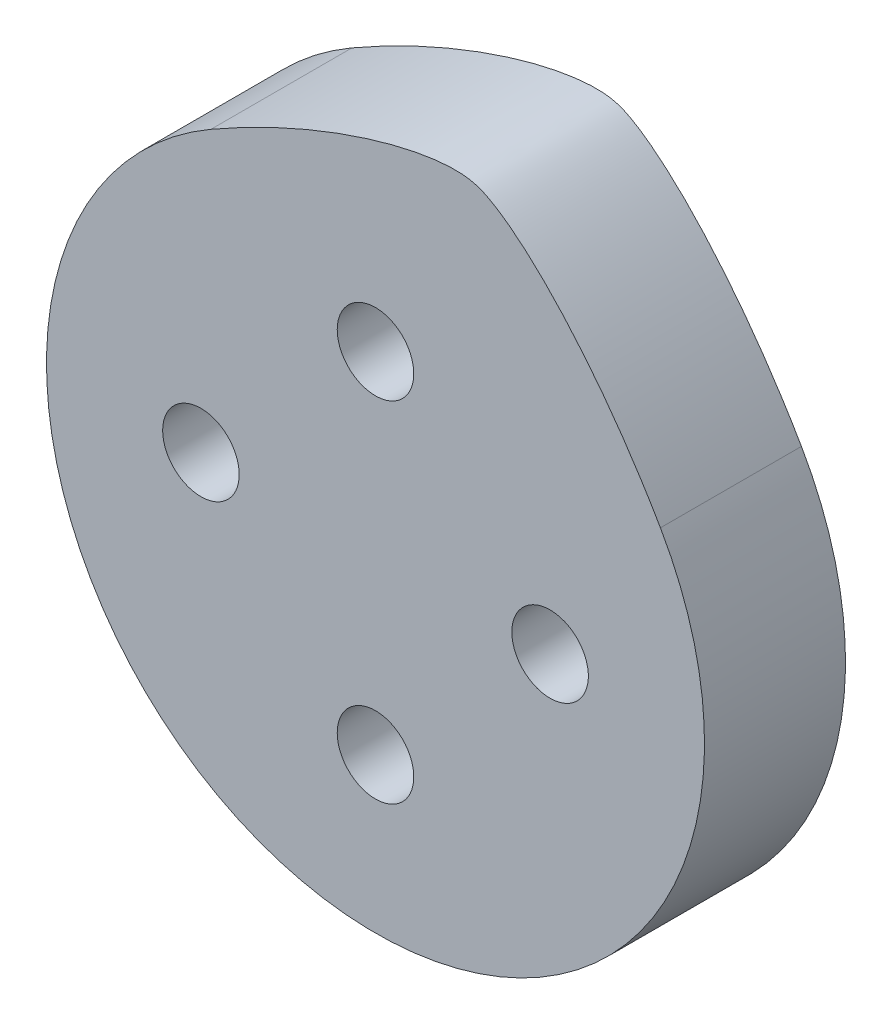
SolidWorks part; units mm, degrees
ref_plane "Front Plane" through (0, 0, 0) normal (1, 0, 0) x (0, 1, 0)
ref_plane "Top Plane" through (0, 0, 0) normal (0, 0, 1) x (0, 1, 0)
ref_plane "Right Plane" through (0, 0, 0) normal (0, 1, 0) x (-1, 0, 0)
sketch "Sketch1" plane through (0, 0, 0) normal (0, 0, 1) x (0, 1, 0)
  circle A0 centre (0, 0) radius 21
  circle A1 centre (0, 0) radius 13 construction
  circle A2 centre (0, 13) radius 1.6
  circle A3 centre (0, 13) radius 2.85
  circle A4 centre (13, 0) radius 2.85
  circle A5 centre (13, 0) radius 1.6
  circle A6 centre (0, -13) radius 2.85
  circle A7 centre (0, -13) radius 1.6
  circle A8 centre (-13, 0) radius 2.85
  circle A9 centre (-13, 0) radius 1.6
  point P19 (0, 0)
  dimension "D1" = 42
  dimension "D2" = 26
  dimension "D3" = 3.2
  dimension "D4" = 5.7
  dimension "D5" = 4
extrude "Boss-Extrude1" add sketch "Sketch1" along normal blind 10.5 contours A0 A8 A6 A4 A3 | A8 A9 | A3 A2 | A4 A5 | A6 A7 region at (0, 0, 0) region at (-13, -2.7694, 0) region at (0, 10.2306, 0) region at (13, -2.7694, 0) region at (0, -15.7694, 0)
sketch "Sketch2" plane through (0, 0, 0) normal (0, 0, -1) x (1, 0, 0)
  line L0 (0, 0) -> (0, 28.5) construction
  line L1 (0, 0) -> (7.3763, -27.5289) construction
  line L2 (0, 0) -> (-14.25, -24.6817) construction
  line L3 (0, 0) -> (24.6817, -14.25) construction
  line L4 (5.6065, -28.0031) -> (-33.0305, -38.3559) construction
  line L5 (23.4579, -41.8336) -> (-80.4652, 18.1664) construction
  line L6 (41.8336, 23.4579) -> (-18.1664, -80.4652) construction
  circle A0 centre (0, 0) radius 28.5 construction
  circle A1 centre (0, 0) radius 24.5
  spline S0 degree 3 poles (-12.25, -21.2176) (-4.4558, -25.7176) (4.5495, -28.3279) (10.224, -26.8074) (16.7176, -20.0442) (21.2176, -12.25) knots 0 0 0 0 0.45 0.55 1 1 1 1
  circle M5 centre (0, 0) radius 21
  dimension "D1" = 57
  dimension "D2" = 49
  dimension "D6" = 20
  dimension "D7" = 30
  dimension "D8" = 30
  dimension "D3" = 165
  dimension "D4" = 45
  dimension "D5" = 45
  dimension "D9" = 90
  dimension "D10" = 90
  dimension "D11" = 90
extrude "Boss-Extrude3" add sketch "Sketch2" against normal up to surface (10.5 mm away) contours A1 M5 | A1 S0 region at (22.9958, 6.1617, 0) region at (6.501, 24.2373, 0) up to face at (21, 0, 10.5)
sketch "Sketch3" plane through (0, 0, 0) normal (0, 0, -1) x (1, 0, 0)
  circle A0 centre (0, 0) radius 21
  circle A5 centre (-13, 0) radius 1.6
  circle A6 centre (0, 13) radius 1.6
  circle A7 centre (13, 0) radius 1.6
  circle A8 centre (0, -13) radius 1.6
  dimension "D1" = 42
extrude "Boss-Extrude4" add sketch "Sketch3" along normal blind 0.5
sketch "Sketch4" plane through (0, 0, 10.5) normal (0, 0, 1) x (1, 0, 0)
  circle A5 centre (-13, 0) radius 1.6
  circle A6 centre (0, 13) radius 1.6
  circle A7 centre (13, 0) radius 1.6
  circle A8 centre (0, -13) radius 1.6
  circle A9 centre (0, 13) radius 2.85
  circle A10 centre (13, 0) radius 2.85
  circle A11 centre (0, -13) radius 2.85
  circle A12 centre (-13, 0) radius 2.85
  dimension "D1" = 5.7
  dimension "D2" = 5.7
  dimension "D3" = 5.7
  dimension "D4" = 5.7
extrude "Cut-Extrude1" cut sketch "Sketch4" against normal blind 8.5 and the other way through all
